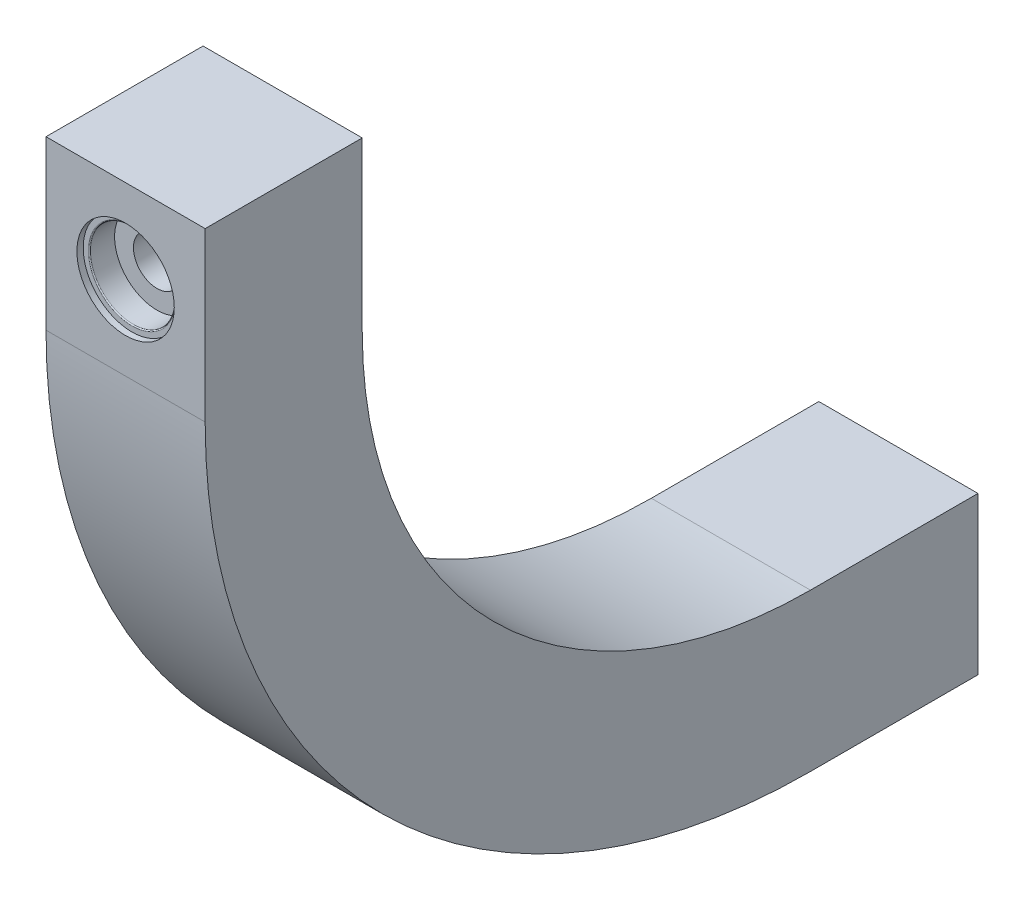
SolidWorks part; units mm, degrees
ref_plane "Front Plane" through (0, 0, 0) normal (0, 0, 1) x (1, 0, 0)
ref_plane "Top Plane" through (0, 0, 0) normal (0, 1, 0) x (1, 0, 0)
ref_plane "Right Plane" through (0, 0, 0) normal (1, 0, 0) x (0, 0, -1)
ref_axis "Z" through (0, 0, 109.5585) along (0, 0, -1)
ref_axis "X" through (8.36, 0, 0) along (-1, 0, 0)
sketch "Sketch4" plane through (0, 0, 0) normal (0, 0, 1) x (1, 0, 0)
  circle A0 centre (0, 0) radius 49.8046 construction
  dimension "D1" = 99.6092
sketch "Sketch5" plane through (0, 0, 0) normal (1, 0, 0) x (0, 0, -1)
  line L0 (-50.8046, 8) -> (-50.8046, 0)
  line L1 (-50.8046, 0) -> (-50.8046, -8)
  line L2 (-65.8046, -8) -> (-65.8046, 8)
  line L6 (-65.8046, 8) -> (-50.8046, 8)
  line L12 (-109.5585, 0) -> (-13.0351, 0) construction
  line L13 (0, 0) -> (-14.9091, -14.9091) construction
  line L14 (0, 0) -> (7.0065, 0) construction
  line L15 (0, -50.8046) -> (-8, -50.8046)
  line L16 (8, -50.8046) -> (0, -50.8046)
  line L17 (-8, -65.8046) -> (8, -65.8046)
  line L18 (8, -65.8046) -> (8, -50.8046)
  circle A0 centre (0, 0) radius 14 construction
  arc A1 (-50.8046, -8) -> (-8, -50.8046) centre (-8, -8) ccw
  arc A2 (-65.8046, -8) -> (-8, -65.8046) centre (-8, -8) ccw
  point P2 (9.4307, -21)
  point P4 (0, -2.1363)
  dimension "D1" = 28
  dimension "D4" = 8
  dimension "D2" = 45
  dimension "D3" = 15
  dimension "D5" = 50.8046
sketch "Sketch6" plane through (0, 0, 0) normal (0, 1, 0) x (1, 0, 0)
  circle A0 centre (0, 0) radius 49.8046 construction
  dimension "D1" = 99.6092
extrude "Boss-Extrude1" add sketch "Sketch5" along normal blind 7.6 and the other way blind 7.6
sketch "Sketch7" plane through (0, 0, 0) normal (0, 0, 1) x (1, 0, 0)
  circle A0 centre (0, 0) radius 2.25
  dimension "D1" = 4.5
extrude "Cut-Extrude1" cut sketch "Sketch7" along normal through all
ref_axis "Y" through (0, -9.3489, 0) along (0, -1, 0)
sketch "Sketch16" plane through (0, 0, 0) normal (1, 0, 0) x (0, 0, -1)
  line L0 (0, -66.8046) -> (0, 0) construction
  dimension "D1" = 66.8046
ref_plane "Plane1" through (0, -66.8046, 0) normal (0, 1, 0) x (1, 0, 0)
ref_axis "CX" through (0, -66.8046, 4.4) along (0, 0, -1)
ref_plane "Plane2" through (0, 0, 0) normal (0, 0, -1) x (0, 1, 0)
ref_plane "Plane3" through (0, 0, 0) normal (1, 0, 0) x (0, 0, -1)
ref_axis "CZ" through (0, -8.7018, 0) along (0, -1, 0)
ref_axis "CY" through (-0.6471, -66.8046, 0) along (1, 0, 0)
ref_point "CO"
sketch "Sketch15" plane through (0, -65.8046, 0) normal (0, -1, 0) x (1, 0, 0)
  circle A0 centre (0, 0) radius 2.05
  dimension "D1" = 4.1
extrude "Cut-Extrude11" cut sketch "Sketch15" against normal blind 10
sketch "Sketch18" plane through (0, 0, 0) normal (1, 0, 0) x (0, 0, -1)
  line L0 (-65.8046, 4.65) -> (-65.8046, 0)
  line L1 (-65.8046, 0) -> (-62.8046, 0)
  line L2 (-62.8046, 0) -> (-62.8046, 4.05)
  line L3 (-62.8046, 4.05) -> (-65.1046, 4.05)
  line L4 (-65.2046, 4.15) -> (-65.2046, 4.65)
  line L5 (-65.2046, 4.65) -> (-65.8046, 4.65)
  line L6 (-68.6876, 0) -> (-58.3046, 0) construction
  line L7 (-58.3046, 0) -> (-58.3046, 8) construction
  line L8 (-51.4046, 4.65) -> (-50.8046, 4.65)
  line L9 (-51.4046, 4.15) -> (-51.4046, 4.65)
  line L10 (-53.8046, 4.05) -> (-51.5046, 4.05)
  line L11 (-53.8046, 0) -> (-53.8046, 4.05)
  line L12 (-50.8046, 0) -> (-53.8046, 0)
  line L13 (-50.8046, 4.65) -> (-50.8046, 0)
  line L14 (-109.5585, 0) -> (-13.0351, 0) construction
  line L15 (-65.8046, 8) -> (-50.8046, 8) construction
  line L16 (-65.8046, -8) -> (-65.8046, 8) construction
  arc A0 (-65.1046, 4.05) -> (-65.2046, 4.15) centre (-65.1046, 4.15) cw
  arc A1 (-51.5046, 4.05) -> (-51.4046, 4.15) centre (-51.5046, 4.15) ccw
  point P23 (-65.2046, 4.05)
  point P26 (-51.4046, 4.05)
  dimension "D5" = 0.1
  dimension "D6" = 0.1
  dimension "D1" = 0.6
  dimension "D2" = 8.1
  dimension "D3" = 3
  dimension "D4" = 4.65
revolve "Cut-Revolve1" cut sketch "Sketch18" angle 360 about axis through (0, 0, 109.5585) along (0, 0, -1)
equation "\"rbracket-width\"= \"L2Thickness\" + 0.2"
equation "\"EyeCaptureRadius\"= ( \"EyeDiameter\" + \"EyeClearance\" ) / 2"
equation "\"rbracket_planetocenterline_dist\"= \"BasePlaneDistance\""
equation "\"EyeDiameter\" = 99.60916292"
equation "\"BasePlaneDistance\" = \"EyeDiameter\"/2+\"L2Thickness\"+\"EyeClearance\""
equation "\"EyeClearance\" = 2"
equation "\"D1@Sketch4\"=\"EyeDiameter\""
equation "\"D1@Sketch6\"=\"EyeDiameter\""
equation "\"D1@Boss-Extrude1\"=\"rbracket-width\"/2"
equation "\"D2@Boss-Extrude1\"=\"rbracket-width\"/2"
equation "\"L2Thickness\" = 3.75 * \"shaft_diameter\""
equation "\"D3@Sketch5\"=\"L2Thickness\""
equation "\"D5@Sketch5\"=(\"EyeDiameter\"+\"EyeClearance\")/2"
equation "\"BearingThickness\"= 6"
equation "\"BearingOD\"=4.5"
equation "\"OuterBearingProudDistance\"= 0"
equation "\"FlangeOD\"=7.5"
equation "\"FlangeThickness\"= 0.75"
equation "\"PrinterFilamentThickness\"= 0.1'For setting distances for things like pressfits"
equation "\"ApplyPrinterOffset\"= 1'Set to 0 for line-to-line. Set to 1 for applying guestimate dimensions to make the printer produce good parts"
equation "\"D1@Cut-Extrude11\"=\"shaft_diameter\"*2.5"
equation "\"D1@Sketch16\"=\"BasePlaneDistance\""
equation "\"D2@Sketch18\"=\"ApplyPrinterOffset\"*\"PrinterFilamentThickness\" + 8"
equation "\"D4@Sketch18\"=4.6 + \"ApplyPrinterOffset\"*\"PrinterFilamentThickness\"/2"
equation "\"L2_ID\" = 20"
equation "\"vx\" = 0"
equation "\"vy\" = 0"
equation "\"vz\" = 200"
equation "\"parametric_end\" = 1"
equation "\"Rw_3_xx\" = -(\"vz\")/sqr((\"vx\")^2 + (\"vz\")^2)"
equation "\"Rw_3_xy\" = 0"
equation "\"Rw_3_xz\" = (\"vx\")/sqr((\"vx\")^2 + (\"vz\")^2)"
equation "\"Rw_3_zx\" = (\"vx\")/sqr((\"vx\")^2 + (\"vy\")^2 + (\"vz\")^2)"
equation "\"Rw_3_zy\" = (\"vy\")/sqr((\"vx\")^2 + (\"vy\")^2 + (\"vz\")^2)"
equation "\"Rw_3_zz\" = (\"vz\")/sqr((\"vx\")^2 + (\"vy\")^2 + (\"vz\")^2)"
equation "\"Rw_3_yx\" = (\"vx\")*(\"vy\")/sqr((\"vx\")^4 + (\"vx\")^2*(\"vy\")^2 + 2*(\"vx\")^2*(\"vz\")^2 + (\"vy\")^2*(\"vz\")^2 + (\"vz\")^4)"
equation "\"Rw_3_yy\" = -sqr((\"vx\")^2 + (\"vz\")^2)/sqr((\"vx\")^2 + (\"vy\")^2 + (\"vz\")^2)"
equation "\"Rw_3_yz\" = (\"vy\")*(\"vz\")/sqr((\"vx\")^4 + (\"vx\")^2*(\"vy\")^2 + 2*(\"vx\")^2*(\"vz\")^2 + (\"vy\")^2*(\"vz\")^2 + (\"vz\")^4)"
equation "\"O2Targx\" = -\"BasePlaneDistance\"*(\"vx\")*(\"vy\")/sqr((\"vx\")^4 + (\"vx\")^2*(\"vy\")^2 + 2*(\"vx\")^2*(\"vz\")^2 + (\"vy\")^2*(\"vz\")^2 + (\"vz\")^4)"
equation "\"O2Targy\" = \"BasePlaneDistance\"*sqr((\"vx\")^2 + (\"vz\")^2)/sqr((\"vx\")^2 + (\"vy\")^2 + (\"vz\")^2)"
equation "\"O2Targz\" = -\"BasePlaneDistance\"*(\"vy\")*(\"vz\")/sqr((\"vx\")^4 + (\"vx\")^2*(\"vy\")^2 + 2*(\"vx\")^2*(\"vz\")^2 + (\"vy\")^2*(\"vz\")^2 + (\"vz\")^4)"
equation "\"O2Targx_0\" = -(\"BasePlaneDistance\")*sqr((\"vx\")^2 + (\"vz\")^2)/sqr((\"vx\")^2 + (\"vy\")^2 + (\"vz\")^2)"
equation "\"O2Targy_0\" = -(\"BasePlaneDistance\")*(\"vy\")*(\"vz\")/sqr((\"vx\")^4 + (\"vx\")^2*(\"vy\")^2 + 2*(\"vx\")^2*(\"vz\")^2 + (\"vy\")^2*(\"vz\")^2 + (\"vz\")^4)"
equation "\"O2Targz_0\" = (\"BasePlaneDistance\")*(\"vx\")*(\"vy\")/sqr((\"vx\")^4 + (\"vx\")^2*(\"vy\")^2 + 2*(\"vx\")^2*(\"vz\")^2 + (\"vy\")^2*(\"vz\")^2 + (\"vz\")^4) + (\"BasePlaneDistance\")"
equation "\"theta2_s1\" = arcsin(((\"BasePlaneDistance\") - (\"O2Targz_0\"))/(\"BasePlaneDistance\")) + pi"
equation "\"theta2_s2\" = -arcsin(((\"BasePlaneDistance\") - (\"O2Targz_0\"))/(\"BasePlaneDistance\"))"
equation "\"theta1_s1\" = arcsin((\"O2Targy_0\")/((\"BasePlaneDistance\")*cos((\"Theta2\")))) + pi"
equation "\"theta1_s2\" = -arcsin((\"O2Targy_0\")/((\"BasePlaneDistance\")*cos((\"Theta2\"))))"
equation "\"theta1_s3\" = -arccos(-(\"O2Targx_0\")/((\"BasePlaneDistance\")*cos((\"Theta2\")))) + 2*pi"
equation "\"theta1_s4\" = arccos(-(\"O2Targx_0\")/((\"BasePlaneDistance\")*cos((\"Theta2\"))))"
equation "\"Theta1\" = \"theta1_s2\" 'so far, theta1_s1 and theta1_s4 have agreed, and they agree with the sw constraint solver"
equation "\"Theta2\" = \"theta2_s2\""
equation "\"o2_x\" = -(\"BasePlaneDistance\")*cos((\"Theta1\"))*cos((\"Theta2\"))"
equation "\"o2_y\" = -(\"BasePlaneDistance\")*sin((\"Theta1\"))*cos((\"Theta2\"))"
equation "\"o2_z\" = (\"BasePlaneDistance\")*(sin((\"Theta2\")) + 1)"
equation "\"o1_x\" = (\"BasePlaneDistance\")*sin((\"Theta1\"))"
equation "\"o1_y\" = -(\"BasePlaneDistance\")*cos((\"Theta1\"))"
equation "\"o1_z\" = (\"BasePlaneDistance\")"
equation "\"Actuator1_Theta\" = atn(\"vx\"/\"vz\") 'ik solution for the single link joint"
equation "\"Actuator2_Theta\" = \"Theta1\"  'ik solution for the double link joint"
equation "\"MotorBaseThickness\" = 3 "
equation "\"BaseThickness\" = 3 "
equation "\"EncoderToMagnetAirgap\" = 1 'Encoder to magnet airgap"
equation "\"EncoderHeight\" = 1.192  'Height of the encoder"
equation "\"MagnetThickness\" = 0.5  'Magnet thickness"
equation "\"pcb_thickness\" = 1.6  'Thickness of the PCB"
equation "\"pcb_outer_diameter\" = 32 'the OD of the pcb"
equation "\"shaft_diameter\" = 4"
equation "\"D1@Sketch15\"=\"shaft_diameter\"+\"ApplyPrinterOffset\"*\"PrinterFilamentThickness\""
